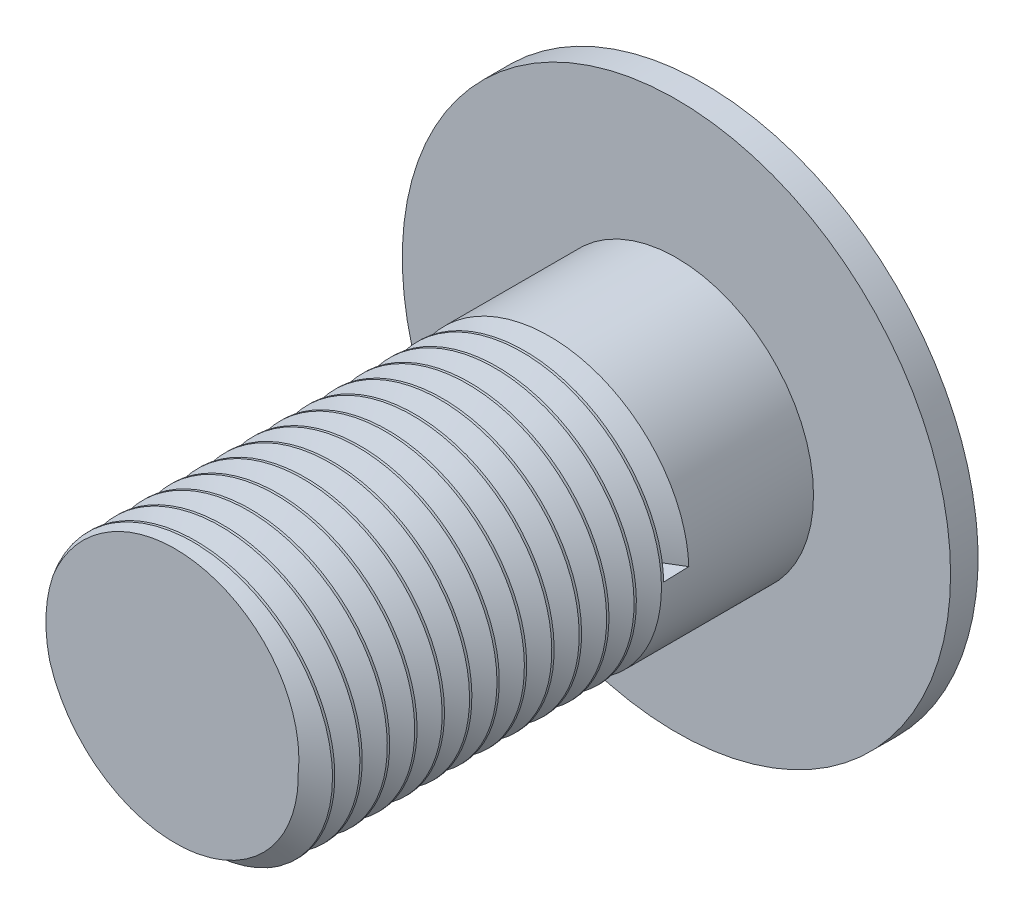
SolidWorks part; units mm, degrees
ref_plane "Front" through (0, 0, 0) normal (0, 0, 1) x (1, 0, 0)
ref_plane "Top" through (0, 0, 0) normal (0, 1, 0) x (1, 0, 0)
ref_plane "Right" through (0, 0, 0) normal (1, 0, 0) x (0, 0, -1)
sketch "Sketch1" plane through (0, 0, 0) normal (0, 0, 1) x (1, 0, 0)
  circle A0 centre (0, 0) radius 2.5
  dimension "D1" = 5
extrude "Boss-Extrude1" add sketch "Sketch1" along normal blind 12
sketch "Sketch2" plane through (0, 0, 0) normal (1, 0, 0) x (0, 0, -1)
  line L0 (0, 0) -> (6.4557, 0) construction
  line L1 (0, 0) -> (0, 5)
  line L2 (0, 5) -> (0.5, 5)
  line L3 (1.8278, 0.693) -> (1.8278, -0.693) construction
  line L4 (0, 0) -> (1.8278, 0)
  spline S0 degree 3 poles (1.8278, 0) (1.8278, 1.8301) (1.5196, 3.4287) (0.5, 5) knots 0 0 0 0 1 1 1 1
  dimension "D1" = 5
  dimension "D2" = 0.5
revolve "Revolve2" add sketch "Sketch2" angle 360 about L4
sketch "Sketch3" plane through (0, 0, 0) normal (0, 0, 1) x (1, 0, 0)
  line L0 (0, 0) -> (6.0499, 0) construction
  line L2 (5.4741, -0.625) -> (-5.5577, -0.625)
  line L3 (5.4741, -0.625) -> (5.4741, 0.625)
  line L4 (5.4741, 0.625) -> (-5.5577, 0.625)
  line L5 (-5.5577, -0.625) -> (-5.5577, 0.625)
  point P7 (5.4741, 0)
  dimension "D1" = 1.25
ref_plane "Plane1" through (0, 0, -0.5) normal (0, 0, 1) x (1, 0, 0)
sketch "Sketch4" plane through (0, 0, -0.5) normal (0, 0, 1) x (1, 0, 0)
  line L4 (-5.5577, -0.625) -> (5.4741, -0.625)
  line L5 (-5.5577, 0.625) -> (-5.5577, -0.625)
  line L6 (5.4741, 0.625) -> (-5.5577, 0.625)
  line L7 (5.4741, -0.625) -> (5.4741, 0.625)
  line L8 (-5.5577, -0.625) -> (5.4741, -0.625)
  line L9 (-5.5577, 0.625) -> (-5.5577, -0.625)
  line L10 (5.4741, 0.625) -> (-5.5577, 0.625)
  line L11 (5.4741, -0.625) -> (5.4741, 0.625)
  dimension "D1" = 0
extrude "Cut-Extrude1" cut sketch "Sketch4" against normal blind 2
sketch "Sketch5" plane through (0, 0, 12) normal (0, 0, 1) x (1, 0, 0)
  circle A0 centre (0, 0) radius 2.5 construction
  circle A1 centre (0, 0) radius 2.5
curve "Helix/Spiral1" pitch 0.5 height 9.5 radius 2.5 centre (0, 0, 12) axis (0, 0, -1) start towards (1, 0, 0)
ref_plane "Plane2" through (2.5, 0, 12) normal (0, -0.9995, -0.0318) x (-1, 0, 0)
sketch "Sketch6" plane through (2.5, 0, 12) normal (0, -0.9995, -0.0318) x (-1, 0, 0)
  line L1 (-0.0196, -0.2433) -> (0.3961, -0.0033)
  line L2 (0.3961, -0.0033) -> (-0.0196, 0.2367)
  line L3 (-0.0196, 0.2367) -> (-0.0196, -0.2433)
  circle A0 centre (0.119, -0.0033) radius 0.1386 construction
  point P1 (0.119, -0.0033)
  dimension "D1" = 0.48
sweep "Cut-Sweep1" cut profiles "Sketch6" path "Helix/Spiral1" align with end faces yes
sketch "Sketch7" plane through (0, 0, 12) normal (0, 0, 1) x (1, 0, 0)
  circle A0 centre (0, 0) radius 3.9858
extrude "Cut-Extrude2" cut sketch "Sketch7" against normal blind 3
